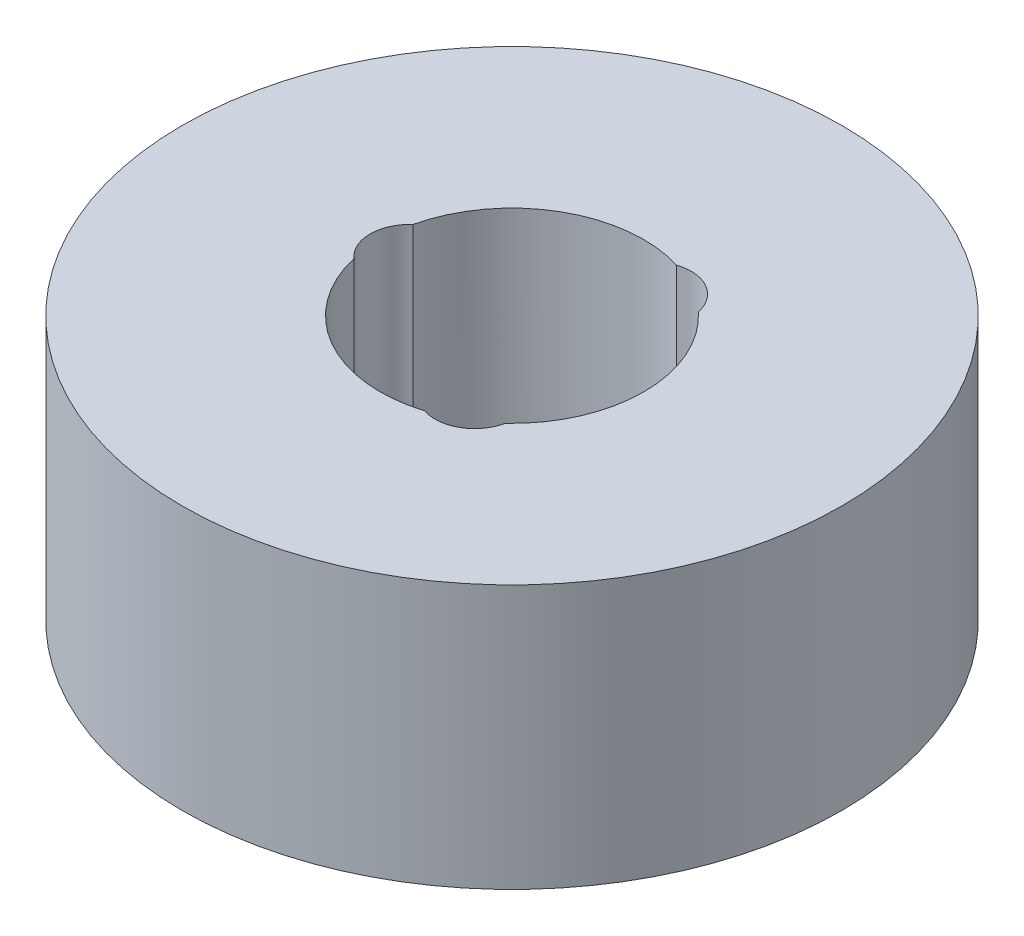
SolidWorks part; units mm, degrees
ref_plane "Front Plane" through (0, 0, 0) normal (0, 0, 1) x (1, 0, 0)
ref_plane "Top Plane" through (0, 0, 0) normal (0, 1, 0) x (1, 0, 0)
ref_plane "Right Plane" through (0, 0, 0) normal (1, 0, 0) x (0, 0, -1)
sketch "Sketch1" plane through (0, 0, 0) normal (0, 1, 0) x (1, 0, 0)
  circle A0 centre (0, 0) radius 12.5
  dimension "FLANGE_OD" = 25
extrude "Boss-Extrude1" add sketch "Sketch1" along normal blind 10
sketch "Sketch2" plane through (0, 0, 0) normal (0, 1, 0) x (1, 0, 0)
  circle A0 centre (0, 0) radius 5
  dimension "BORE_D" = 10
extrude "Cut-Extrude1" cut sketch "Sketch2" along normal through all
sketch "Sketch3" plane through (0, 10, 0) normal (0, 1, 0) x (1, 0, 0)
  circle A0 centre (0, 0) radius 3.8759 construction
  circle A1 centre (-3.8759, 0) radius 1.5
  dimension "BOLT_D" = 3
  dimension "BOLT_PCD" = 7.7517
extrude "Cut-Extrude2" cut sketch "Sketch3" against normal blind 8.4415
pattern_circular "CirPattern1" count 3 over 360 about axis through (0, 0, 0) along (0, 1, 0) of "Cut-Extrude2"
